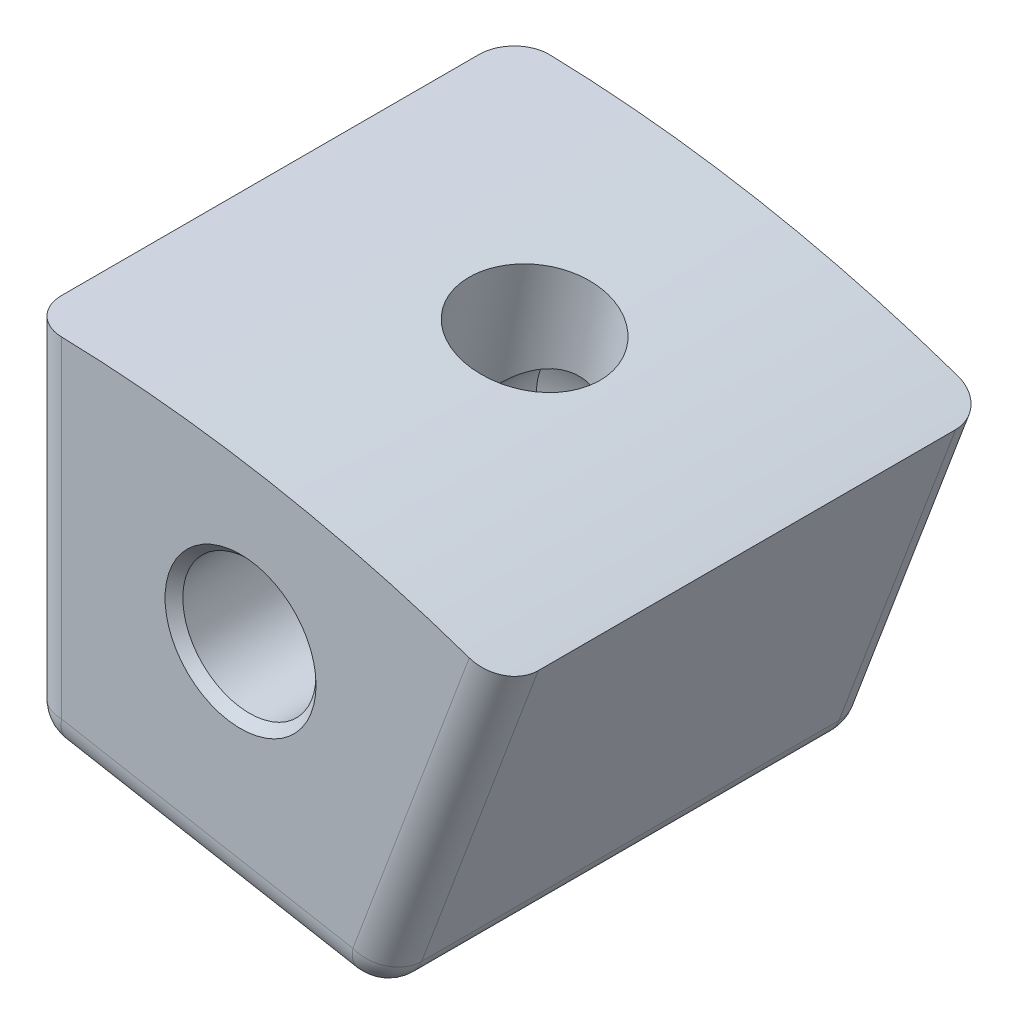
SolidWorks part; units mm, degrees
material "6061-T6 (SS)"
ref_plane "Front Plane" through (0, 0, 0) normal (0, 0, 1) x (1, 0, 0)
ref_plane "Top Plane" through (0, 0, 0) normal (0, 1, 0) x (1, 0, 0)
ref_plane "Right Plane" through (0, 0, 0) normal (1, 0, 0) x (0, 0, -1)
sketch "Sketch1" plane through (0, 0, 0) normal (0, 0, 1) x (1, 0, 0)
  line L0 (0, 96.8375) -> (0, 71.0214)
  line L1 (34.0746, 90.6445) -> (24.9906, 66.4794)
  line L2 (0, 71.0214) -> (0, 83.9294)
  line L3 (0, 71.0214) -> (24.9906, 66.4794)
  circle A0 centre (0, 0) radius 96.8375
  dimension "D1" = 25.4
  dimension "D4" = 193.675
  dimension "D2" = 25.4
extrude "Boss-Extrude2" add sketch "Sketch1" along normal blind 34.925 contours L1 A0 L0 L3 region at (14.9852, 82.4499, 0)
sketch "Sketch5" plane through (0, 0, 34.925) normal (0, 0, 1) x (1, 0, 0)
  line L1 (12.4953, 68.7504) -> (17.3164, 95.2767) construction
  line L2 (0, 71.0214) -> (24.9906, 66.4794) construction
  arc A2 (0, 96.8375) -> (34.0746, 90.6445) centre (0, 0) cw
  arc A3 (34.0746, 90.6445) -> (0, 96.8375) centre (0, 0) ccw construction
  point P3 (15.3293, 84.3433)
  dimension "D1" = 85.725
hole_wizard "3/8 (0.3750) Dowel Hole1" positions "3DSketch3" profile "Sketch7" hole size "3/8" standard "ANSI Inch"
sketch3d "3DSketch3"
  point P0 (15.3293, 84.3433, 34.925)
sketch "Sketch7" plane through (15.3293, 84.3433, 34.925) normal (1, 0, 0) x (0, -1, 0)
  line L0 (0, 0) -> (0, 28.7696)
  line L1 (0, 28.7696) -> (4.7625, 25.908)
  line L2 (4.7625, 25.908) -> (4.7625, 0.635)
  line L3 (4.7625, 0.635) -> (5.3975, 0)
  line L5 (5.3975, 0) -> (0, 0)
  line L6 (-4.7625, 0.635) -> (-5.3975, 0) construction
  line L10 (0, 28.7696) -> (-4.7625, 25.908) construction
  line L11 (0, -6.35) -> (0, 107.95) construction
  dimension "Hole Dia." = 9.525
  dimension "Hole Depth" = 25.908
  dimension "Near C'Sink Dia." = 10.795
  dimension "Near C'Sink Angle" = 90
  dimension "Drill Angle" = 118
sketch "Sketch8" plane through (12.4953, 68.7504, 0) normal (-0.1788, -0.9839, 0) x (-0.9839, 0.1788, 0)
  circle A0 centre (0, -12.7) radius 4.7625
extrude "Cut-Extrude1" [suppressed] cut sketch "Sketch8" against normal blind 25.4 contours A0
sketch "Sketch11" [suppressed] plane through (12.6328, 128.2508, 0) normal (-0.098, -0.9952, 0) x (-0.9952, 0.098, 0)
  circle A0 centre (0, -12.7) radius 4.7625
extrude "Boss-Extrude5" [suppressed] add sketch "Sketch11" against normal blind 5.08
ref_plane "Plane1" through (17.3164, 95.2767, 0) normal (0.1788, 0.9839, 0) x (0.9839, -0.1788, 0)
sketch "Sketch12" plane through (17.3164, 95.2767, 0) normal (0.1788, 0.9839, 0) x (0.9839, -0.1788, 0)
  line L0 (17.3164, 0) -> (-17.3164, 0) construction
  circle A0 centre (0, -15.875) radius 4.7625
  dimension "D1" = 9.525
  dimension "D2" = 15.875
extrude "Cut-Extrude2" cut sketch "Sketch12" against normal up to next contours A0
fillet "Fillet1" radius 2.54 1 edges at (0, 83.9294, 34.925)
fillet "Fillet2" radius 2.54 3 edges at (0, 71.0214, 16.1925) (0.7439, 70.8862, 34.1811) (13.7653, 68.5196, 34.925)
fillet "Fillet3" radius 2.54 3 edges at (24.9906, 66.4794, 16.1925) (25.2567, 67.1872, 34.1811) (29.9868, 79.7702, 34.925)
fillet "Fillet4" radius 2.54 5 edges at (0, 84.9894, 0) (0.59, 71.5138, 0) (12.4953, 68.7504, 0) (24.6116, 67.1479, 0) (29.9056, 79.5541, 0)
